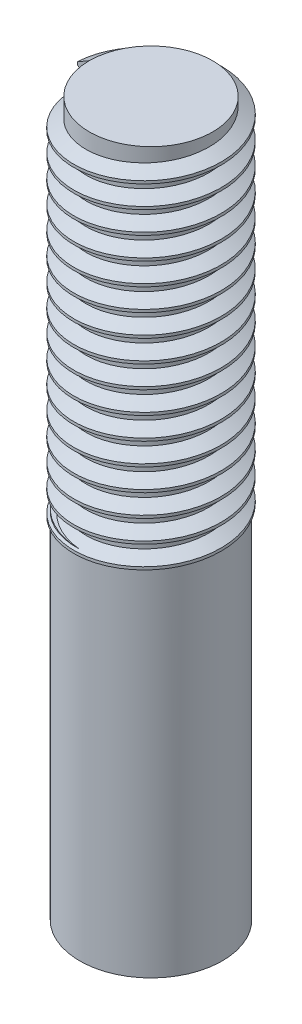
SolidWorks part; units mm, degrees
ref_plane "Front Plane" through (0, 0, 0) normal (0, 0, 1) x (1, 0, 0)
ref_plane "Top Plane" through (0, 0, 0) normal (0, 1, 0) x (1, 0, 0)
ref_plane "Right Plane" through (0, 0, 0) normal (1, 0, 0) x (0, 0, -1)
sketch "Sketch3" plane through (0, 0, 0) normal (0, 0, 1) x (1, 0, 0)
  line L0 (0, 0) -> (0, 40) construction
  line L1 (2.5, 0) -> (2.5, 16)
  line L2 (2.5, 16) -> (0, 17.4434)
  line L3 (0, 17.4434) -> (0, 40)
  line L4 (4, 0) -> (4, 40)
  line L7 (2.5, 0) -> (4, 0)
  line L8 (0, 40) -> (4, 40)
  dimension "D1" = 5
  dimension "D2" = 60
  dimension "D3" = 16
  dimension "D4" = 1.5
  dimension "D7" = 40
revolve "Revolve1" add sketch "Sketch3" angle 360 about L0
sketch "Sketch13" plane through (0, 40, 0) normal (0, 1, 0) x (1, 0, 0)
  circle A0 centre (0, 0) radius 3.46
  circle A2 centre (0, 0) radius 4 construction
  circle A3 centre (0, 0) radius 4
  circle M2 centre (0, 0) radius 4
  dimension "D1" = 6.92
extrude "Cut-Extrude3" cut sketch "Sketch13" against normal blind 20 contours A0 M2 region at (-3.8869, 40, 0)
thread "Thread2" pitch 1.25 method extrude profile "Thread Profile6" start angle 0, offset 0, length 20, pitch 1.25, diameter 6.92
ref_plane "Plane6" through (-3.46, 40, 0) normal (0, 0, 1) x (-1, 0, 0)
sketch "Thread Profile6" plane through (-3.46, 40, 0) normal (0, 0, 1) x (-1, 0, 0)
  line L0 (0, 0) -> (0, 1.25) construction
  line L1 (0, 0) -> (0.6766, 0.3906)
  line L2 (0.6766, 0.3906) -> (0.6766, 0.5469)
  line L3 (0.6766, 0.5469) -> (0, 0.9375)
  line L4 (0.6766, 0.4687) -> (0, 0.4687) construction
  line L11 (0, 0) -> (0, 0.9375)
  point P2 (0, 0)
  dimension "Pitch" = 1.25
  dimension "Profile_Angle" = 60
  dimension "Profile_Land" = 0.1562
  dimension "Profile_Height" = 0.6766
